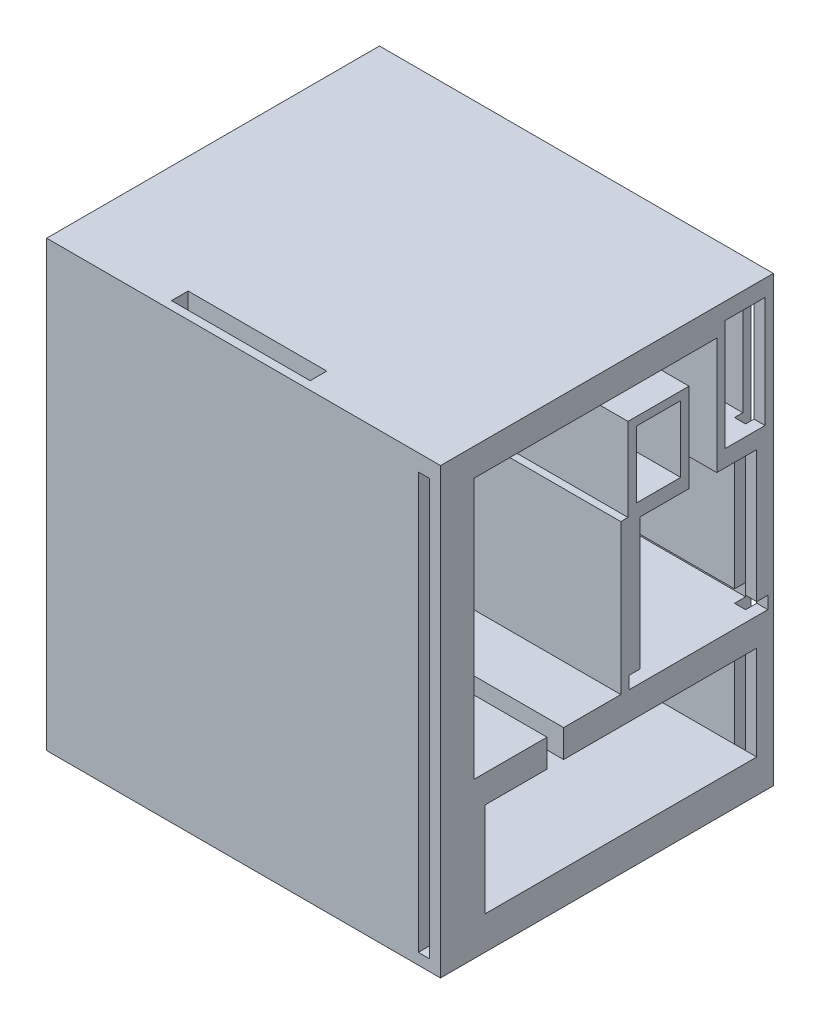
SolidWorks part; units mm, degrees
ref_plane "前视基准面" through (0, 0, 0) normal (0, 0, 1) x (1, 0, 0)
ref_plane "上视基准面" through (0, 0, 0) normal (0, 1, 0) x (1, 0, 0)
ref_plane "右视基准面" through (0, 0, 0) normal (1, 0, 0) x (0, 0, -1)
other "Configuration Table"
sketch "草图1" plane through (0, 0, 0) normal (0, 0, 1) x (1, 0, 0)
  line L1 (-77.0644, 67.339) -> (-2.0644, 67.339)
  line L2 (-77.0644, 67.339) -> (-77.0644, -12.661)
  line L3 (-77.0644, -12.661) -> (-2.0644, -12.661)
  line L4 (-2.0644, 67.339) -> (-2.0644, -12.661)
  dimension "D1" = 80
  dimension "D2" = 75
extrude "凸台-拉伸1" add sketch "草图1" along normal blind 60
sketch "草图2" plane through (-2.0644, 0, 0) normal (1, 0, 0) x (0, 0, -1)
  line L0 (-60, -12.661) -> (0, -12.661) construction
  line L1 (-54, 42.339) -> (-27.5, 42.339)
  line L2 (-54, 42.339) -> (-54, 15.339)
  line L3 (-54, 15.339) -> (-27.5, 15.339)
  line L4 (-27.5, 42.339) -> (-27.5, 15.339)
  line L5 (-24, 41.339) -> (-3, 41.339)
  line L6 (-24, 41.339) -> (-24, 15.339)
  line L7 (-24, 15.339) -> (-3, 15.339)
  line L8 (-3, 41.339) -> (-3, 15.339)
  line L9 (-52, 10.339) -> (-3, 10.339)
  line L10 (-52, 10.339) -> (-52, -6.661)
  line L11 (-52, -6.661) -> (-3, -6.661)
  line L12 (-3, 10.339) -> (-3, -6.661)
  line L21 (-60, -12.661) -> (-60, 67.339) construction
  line L23 (-40.8061, 15.339) -> (-37.8061, 15.339)
  line L24 (-40.8061, 15.339) -> (-40.8061, 10.339)
  line L25 (-40.8061, 10.339) -> (-37.8061, 10.339)
  line L26 (-37.8061, 15.339) -> (-37.8061, 10.339)
  line L31 (-54, 62.339) -> (-26.2, 62.339)
  line L32 (-54, 62.339) -> (-54, 42.339)
  line L33 (-54, 42.339) -> (-26.2, 42.339)
  line L34 (-26.2, 62.339) -> (-26.2, 42.339)
  line L36 (0, -12.661) -> (0, 67.339) construction
  line L37 (-3, 17.589) -> (-1, 17.589)
  line L38 (-26, 17.589) -> (-24, 17.589)
  line L39 (-26, 17.589) -> (-26, 15.339)
  line L40 (-26, 15.339) -> (-24, 15.339)
  line L41 (-24, 17.589) -> (-24, 15.339)
  line L42 (-3, 17.589) -> (-3, 15.339)
  line L43 (-3, 15.339) -> (-1, 15.339)
  line L44 (-1, 17.589) -> (-1, 15.339)
  line L45 (-26.2, 62.339) -> (-10.2, 62.339)
  line L46 (-26.2, 62.339) -> (-26.2, 57.339)
  line L47 (-26.2, 57.339) -> (-10.2, 57.339)
  line L48 (-10.2, 62.339) -> (-10.2, 57.339)
  line L49 (-15.2, 57.339) -> (-10.2, 57.339)
  line L50 (-15.2, 57.339) -> (-15.2, 41.339)
  line L51 (-15.2, 41.339) -> (-10.2, 41.339)
  line L52 (-10.2, 57.339) -> (-10.2, 41.339)
  dimension "D2" = 27
  dimension "D3" = 21
  dimension "D4" = 26
  dimension "D5" = 49
  dimension "D6" = 17
  dimension "D7" = 6
  dimension "D8" = 3
  dimension "D9" = 3
  dimension "D10" = 5
  dimension "D11" = 0
  dimension "D12" = 0
  dimension "D13" = 1
  dimension "D14" = 0
  dimension "D15" = 20
  dimension "D16" = 26.5
  dimension "D17" = 6
  dimension "D23" = 2
  dimension "D24" = 2
  dimension "D25" = 0
  dimension "D26" = 0
  dimension "D29" = 2.25
  dimension "D30" = 2.25
  dimension "D31" = 5
  dimension "D32" = 16
  dimension "D33" = 0
  dimension "D34" = 5
  dimension "D35" = 0
extrude "切除-拉伸2" cut sketch "草图2<3>" against normal blind 70 contours L34 L31 L32 L1 | L48 L45 L34 L47 | L52 L47 L50 L5 region at (-2.0644, 52.339, 40.1) region at (-2.0644, 59.839, 18.2) region at (-2.0644, 49.339, 12.7)
sketch "草图2<3>" plane through (-2.0644, 0, 0) normal (1, 0, 0) x (0, 0, -1) same geometry as "草图2"
extrude "切除-拉伸3" cut sketch "草图2<4>" against normal blind 70 contours L4 L1 L2 L3 region at (-2.0644, 28.839, 40.75)
sketch "草图2<4>" plane through (-2.0644, 0, 0) normal (1, 0, 0) x (0, 0, -1) same geometry as "草图2"
extrude "切除-拉伸4" cut sketch "草图2<5>" against normal blind 50 contours L8 L5 L6 L7 | L38 L41 L40 L39 | L43 L44 L37 L42 region at (-2.0644, 28.339, 13.5)
sketch "草图2<5>" plane through (-2.0644, 0, 0) normal (1, 0, 0) x (0, 0, -1) same geometry as "草图2"
extrude "切除-拉伸5" cut sketch "草图2" against normal blind 70 contours L26 L3 L24 L9 | L12 L9 L10 L11 region at (-2.0644, 12.839, 39.3061) region at (-2.0644, 1.839, 27.5)
sketch "草图4" plane through (0, 0, 0) normal (0, 0, -1) x (-1, 0, 0)
  line L0 (2.0644, -12.661) -> (2.0644, 67.339) construction
  line L1 (4.0644, 64.339) -> (6.0644, 64.339)
  line L2 (4.0644, 64.339) -> (4.0644, -10.661)
  line L3 (4.0644, -10.661) -> (6.0644, -10.661)
  line L4 (6.0644, 64.339) -> (6.0644, -10.661)
  line L6 (2.0644, 67.339) -> (77.0644, 67.339) construction
  dimension "D1" = 2
  dimension "D2" = 2
  dimension "D3" = 75
  dimension "D4" = 3
extrude "切除-拉伸6" cut sketch "草图4" against normal blind 3
sketch "草图6" plane through (0, 67.339, 0) normal (0, 1, 0) x (1, 0, 0)
  line L0 (-2.0644, -60) -> (-77.0644, -60) construction
  line L1 (-52.0644, -55.5) -> (-27.0644, -55.5)
  line L2 (-52.0644, -55.5) -> (-52.0644, -58.5)
  line L3 (-52.0644, -58.5) -> (-27.0644, -58.5)
  line L4 (-27.0644, -55.5) -> (-27.0644, -58.5)
  line L5 (-77.0644, -60) -> (-77.0644, 0) construction
  dimension "D1" = 25
  dimension "D2" = 3
  dimension "D3" = 1.5
  dimension "D4" = 25
extrude "切除-拉伸7" cut sketch "草图6" against normal through all
sketch "草图7" plane through (-52.0644, 0, 0) normal (1, 0, 0) x (0, 0, -1)
  line L0 (-26, 15.339) -> (-1, 15.339) construction
  line L1 (-15.25, 17.339) -> (-12.25, 17.339)
  line L2 (-15.25, 17.339) -> (-15.25, 15.339)
  line L3 (-15.25, 15.339) -> (-12.25, 15.339)
  line L4 (-12.25, 17.339) -> (-12.25, 15.339)
  line L5 (-26, 17.589) -> (-26, 15.339) construction
  dimension "D1" = 3
  dimension "D2" = 10.75
  dimension "D3" = 2
sketch "草图8" plane through (-2.0644, 0, 0) normal (1, 0, 0) x (0, 0, -1)
  line L0 (-60, 67.339) -> (0, 67.339) construction
  line L1 (-24.7, 55.839) -> (-16.7, 55.839)
  line L2 (-24.7, 55.839) -> (-24.7, 43.839)
  line L3 (-24.7, 43.839) -> (-16.7, 43.839)
  line L4 (-16.7, 55.839) -> (-16.7, 43.839)
  line L5 (-8.7, 64.339) -> (-1.5, 64.339)
  line L6 (-8.7, 64.339) -> (-8.7, 44.339)
  line L7 (-8.7, 44.339) -> (-1.5, 44.339)
  line L8 (-1.5, 64.339) -> (-1.5, 44.339)
  line L9 (0, -12.661) -> (0, 67.339) construction
  line L10 (-10.2, 62.339) -> (-10.2, 41.339) construction
  line L11 (-10.2, 41.339) -> (-3, 41.339) construction
  line L12 (-26.2, 57.339) -> (-15.2, 57.339) construction
  line L13 (-26.2, 57.339) -> (-26.2, 42.339) construction
  line L14 (-15.2, 57.339) -> (-15.2, 41.339) construction
  point P22 (-15.2, 49.339)
  dimension "D1" = 3
  dimension "D2" = 1.5
  dimension "D3" = 1.5
  dimension "D4" = 3
  dimension "D5" = 1.5
  dimension "D6" = 1.5
  dimension "D7" = 1.5
extrude "切除-拉伸8" cut sketch "草图7" against normal blind 3
sketch "草图9" plane through (-77.0644, 0, 0) normal (-1, 0, 0) x (0, 0, 1)
  line L0 (60, 67.339) -> (60, -12.661) construction
  line L1 (0, 67.339) -> (60, 67.339)
  line L2 (0, 67.339) -> (0, -12.661)
  line L3 (0, -12.661) -> (60, -12.661)
  line L4 (60, 67.339) -> (60, -12.661)
extrude "切除-拉伸11" cut sketch "草图9" against normal blind 4
sketch "草图10" plane through (0, 0, 60) normal (0, 0, 1) x (1, 0, 0)
  line L0 (-73.0644, -12.661) -> (-2.0644, -12.661) construction
  line L1 (-6.0644, 64.339) -> (-4.0644, 64.339)
  line L2 (-6.0644, 64.339) -> (-6.0644, -10.661)
  line L3 (-6.0644, -10.661) -> (-4.0644, -10.661)
  line L4 (-4.0644, 64.339) -> (-4.0644, -10.661)
  line L5 (-2.0644, -12.661) -> (-2.0644, 67.339) construction
  dimension "D1" = 75
  dimension "D2" = 2
  dimension "D3" = 2
  dimension "D4" = 2
extrude "切除-拉伸12" cut sketch "草图10" against normal blind 3
extrude "切除-拉伸13" cut sketch "草图8" against normal blind 70
